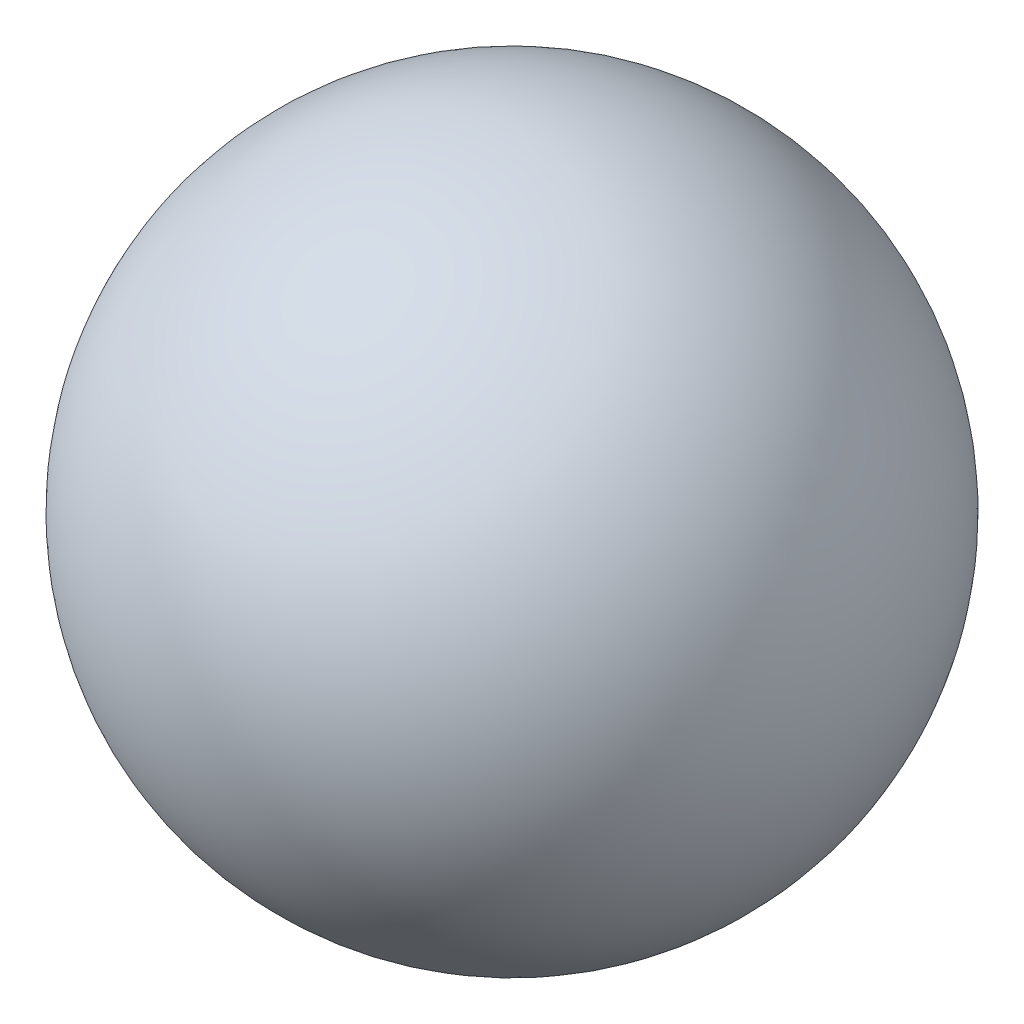
SolidWorks part; units mm, degrees
ref_plane "Front Plane" through (0, 0, 0) normal (0, 0, 1) x (1, 0, 0)
ref_plane "Top Plane" through (0, 0, 0) normal (0, 1, 0) x (1, 0, 0)
ref_plane "Right Plane" through (0, 0, 0) normal (1, 0, 0) x (0, 0, -1)
sketch "Sketch1" plane through (0, 0, 0) normal (0, 1, 0) x (1, 0, 0)
  line L0 (-210348.45, 0) -> (210348.45, 0)
  arc A0 (-210348.45, 0) -> (210348.45, 0) centre (0, 0) ccw
  dimension "D1" = 420696.9
ref_axis "Axis1" through (-231383.295, 0, 0) along (1, 0, 0)
revolve "Revolve5" add sketch "Sketch1" angle 360 about L0
